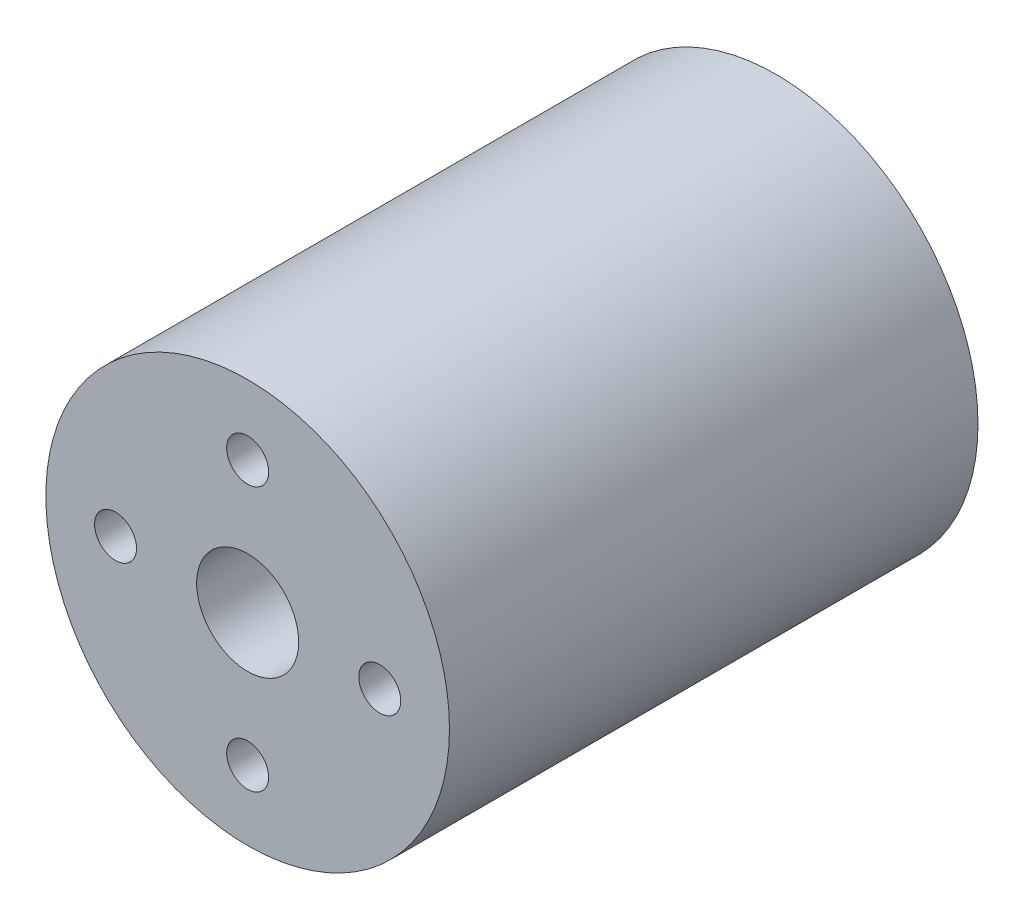
SolidWorks part; units mm, degrees
material "AISI 316 Annealed Stainless Steel Bar (SS)"
ref_plane "Front Plane" through (0, 0, 0) normal (1, 0, 0) x (0, 1, 0)
ref_plane "Top Plane" through (0, 0, 0) normal (0, 0, 1) x (0, 1, 0)
ref_plane "Right Plane" through (0, 0, 0) normal (0, 1, 0) x (-1, 0, 0)
sketch "Sketch1" plane through (0, 0, 0) normal (0, 0, 1) x (0, 1, 0)
  line L0 (0, 7.5) -> (0, -7.5) construction
  line L1 (-7.5, 0) -> (7.5, 0) construction
  circle A0 centre (0, 0) radius 11.455
  circle A1 centre (0, 0) radius 2.8956
  circle A2 centre (0, 7.5) radius 1.1906
  circle A3 centre (-7.5, 0) radius 1.1906
  circle A4 centre (7.5, 0) radius 1.1906
  circle A5 centre (0, -7.5) radius 1.1906
  point P12 (0, 0)
  dimension "D1" = 22.91
  dimension "D2" = 5.7912
  dimension "D3" = 2.3812
  dimension "D4" = 15
extrude "Boss-Extrude1" add sketch "Sketch1" against normal blind 30 contours A0 A5 A4 A3 A2 A1 | A3 | A2 | A4 | A5 | A1 region at (0, -11.131, 0) region at (0, 0, 0) region at (-7.5, 0, 0) region at (0, -7.5, 0) region at (0, 7.5, 0) region at (7.5, 0, 0)
extrude "Cut-Extrude1" cut sketch "Sketch1<3>" against normal blind 8 contours A2 | A3 | A4 | A5 region at (-7.5, 0, 0) region at (0, -7.5, 0) region at (0, 7.5, 0) region at (7.5, 0, 0)
sketch "Sketch1<3>" plane through (0, 0, 0) normal (0, 0, 1) x (0, 1, 0) same geometry as "Sketch1"
extrude "Cut-Extrude2" cut sketch "Sketch1<4>" against normal blind 16 contours A1 region at (0, 0, 0)
sketch "Sketch1<4>" plane through (0, 0, 0) normal (0, 0, 1) x (0, 1, 0) same geometry as "Sketch1"
